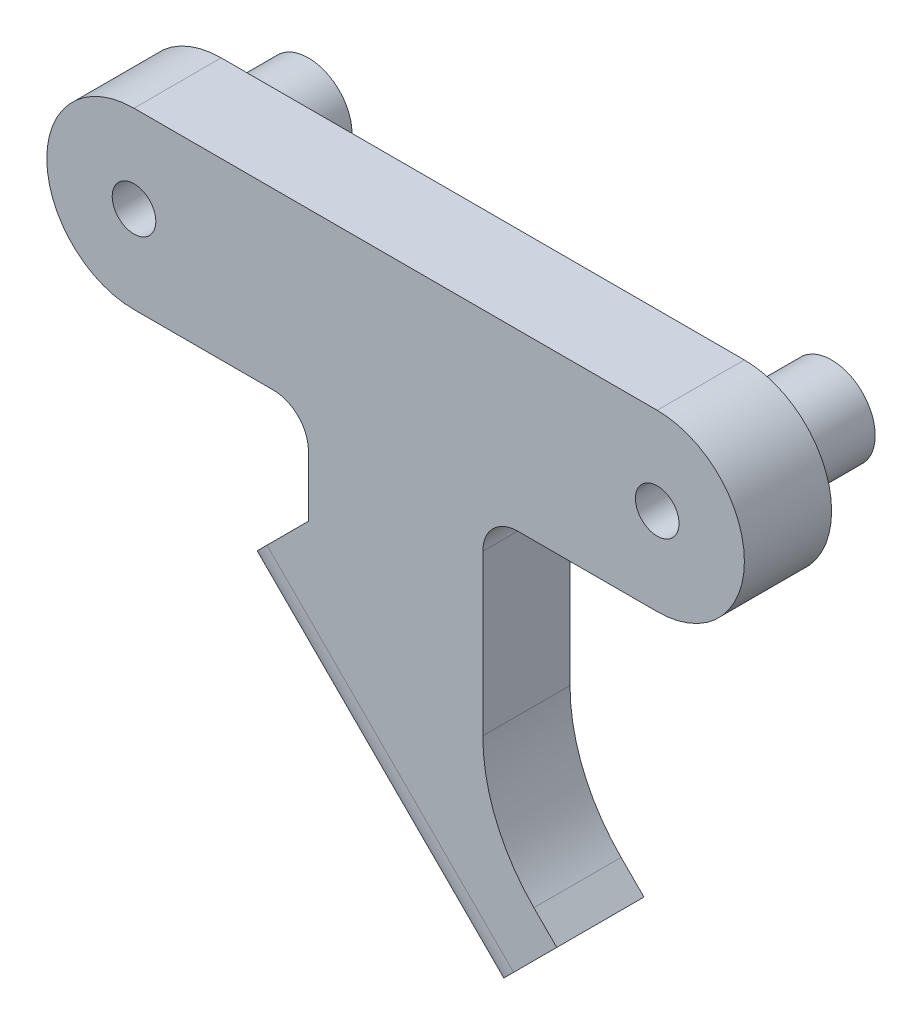
SolidWorks part; units mm, degrees
material "PET"
ref_plane "Piano frontale" through (0, 0, 0) normal (0, 0, 1) x (1, 0, 0)
ref_plane "Piano superiore" through (0, 0, 0) normal (0, 1, 0) x (1, 0, 0)
ref_plane "Piano destro" through (0, 0, 0) normal (1, 0, 0) x (0, 0, -1)
sketch "Schizzo1" plane through (0, 0, 0) normal (0, 0, 1) x (1, 0, 0)
  line L1 (-13.208, 5) -> (16.792, 5)
  line L2 (-13.208, -5) -> (-3.208, -5)
  line L3 (6.792, -28.7941) -> (6.792, -18.7941)
  line L4 (-3.208, -18.7941) -> (6.792, -28.7941)
  line L5 (6.792, -5) -> (16.792, -5)
  line L7 (-3.208, -5) -> (-3.208, -18.7941)
  line L9 (6.792, -5) -> (6.792, -18.7941)
  line L10 (6.792, 0) -> (16.792, 0) construction
  arc A0 (-13.208, 5) -> (-13.208, -5) centre (-13.208, 0) ccw
  arc A1 (16.792, -5) -> (16.792, 5) centre (16.792, 0) ccw
  point P3 (1.792, 0)
  dimension "D1" = 30
  dimension "D2" = 10
  dimension "D3" = 10
  dimension "D4" = 10
extrude "Estrusione-Estrusione3" add sketch "Schizzo1" along normal blind 5 contours L2 L7 L4 L3 L9 L5 A1 L1 A0
sketch "Schizzo3" plane through (0, 0, 0) normal (0, 0, -1) x (-1, 0, 0)
  line L6 (13.208, 5) -> (-16.792, 5)
  line L7 (-16.792, -5) -> (-6.792, -5)
  line L8 (-6.792, -5) -> (-6.792, -28.7941)
  line L9 (-6.792, -28.7941) -> (3.208, -18.7941)
  line L10 (3.208, -18.7941) -> (3.208, -5)
  line L11 (3.208, -5) -> (13.208, -5)
  line L12 (13.208, 5) -> (-16.792, 5) construction
  line L13 (-16.792, -5) -> (-6.792, -5) construction
  line L14 (-6.792, -5) -> (-6.792, -28.7941) construction
  line L15 (-6.792, -28.7941) -> (3.208, -18.7941) construction
  line L16 (3.208, -18.7941) -> (3.208, -5) construction
  line L17 (3.208, -5) -> (13.208, -5) construction
  circle A0 centre (-16.792, 0) radius 2.5
  circle A1 centre (13.208, 0) radius 2.5
  arc A2 (13.208, -5) -> (13.208, 5) centre (13.208, 0) ccw
  arc A3 (-16.792, 5) -> (-16.792, -5) centre (-16.792, 0) ccw
  arc A4 (13.208, -5) -> (13.208, 5) centre (13.208, 0) ccw construction
  arc A5 (-16.792, 5) -> (-16.792, -5) centre (-16.792, 0) ccw construction
  dimension "D1" = 0
extrude "Estrusione-Estrusione4" add sketch "Schizzo3" along normal blind 5
ref_plane "Piano1" through (17.7931, -17.7931, 0) normal (-0.7071, 0.7071, 0) x (0, 0, -1)
sketch "Schizzo7" plane through (17.7931, -17.7931, 0) normal (-0.7071, 0.7071, 0) x (0, 0, -1)
  line L0 (-5, 15.5578) -> (-5, -1.2671) construction
  line L1 (0, 15.5578) -> (-5, 15.5578)
  line L2 (0, 15.5578) -> (0, 9.5578)
  line L3 (0, 9.5578) -> (-5, 9.5578)
  line L4 (-5, 15.5578) -> (-5, 9.5578)
  dimension "D1" = 6
extrude "Estrusione-Estrusione5" add sketch "Schizzo7" along normal blind 20
sketch "Schizzo6" plane through (17.7931, -17.7931, 0) normal (-0.7071, 0.7071, 0) x (0, 0, -1)
  line L0 (0, -1.2671) -> (0, 9.5578) construction
  line L1 (-5, 15.5578) -> (0, 15.5578) construction
  circle A0 centre (-2.5, 12.5578) radius 1.65
  dimension "D1" = 3.3
  dimension "D2" = 2.5
  dimension "D3" = 3
extrude "Taglio-Estrusione1" cut sketch "Schizzo6" along normal up to surface (20 mm away) up to face at (-5.2791, -12.5809, 2.5)
fillet "Raccordo1" radius 2.5 2 edges at (-0.2791, -21.723, 0) (-0.2791, -21.723, 5)
sketch "Schizzo8" plane through (0, 0, -5) normal (0, 0, -1) x (-1, 0, 0)
  circle A0 centre (-16.792, 0) radius 1.25
  circle A1 centre (13.208, 0) radius 1.25
  dimension "D1" = 2.5
extrude "Taglio-Estrusione2" cut sketch "Schizzo8" against normal through all
fillet "Raccordo2" radius 2 2 edges at (-3.208, -5, 2.5) (6.792, -5, 2.5)
fillet "Raccordo3" radius 10 1 edges at (6.792, -20.3088, 2.5)
ref_axis "Assi1" through (-5.2288, -12.5306, 2.5) along (0.7071, -0.7071, 0)
ref_point "Punto1"
ref_axis "Assi2" through (11.0346, -24.5515, 5) along (0, 0, -1)
ref_point "Punto2"
ref_axis "Assi3" through (16.792, 0, 5) along (0, 0, -1)
ref_axis "Assi4" through (6.792, -7, 0) along (0, -1, 0)
ref_point "Punto3"
sketch "Schizzo9" plane through (0, 0, 0) normal (0, 0, -1) x (-1, 0, 0)
  line L0 (-16.792, 0) -> (13.208, 0)
  line L1 (-1.792, 0) -> (-1.792, -20.2586)
  line L2 (-8.5598, -27.0263) -> (5.5824, -12.8842) construction
  point P4 (-1.792, 0)
ref_point "Punto4"
